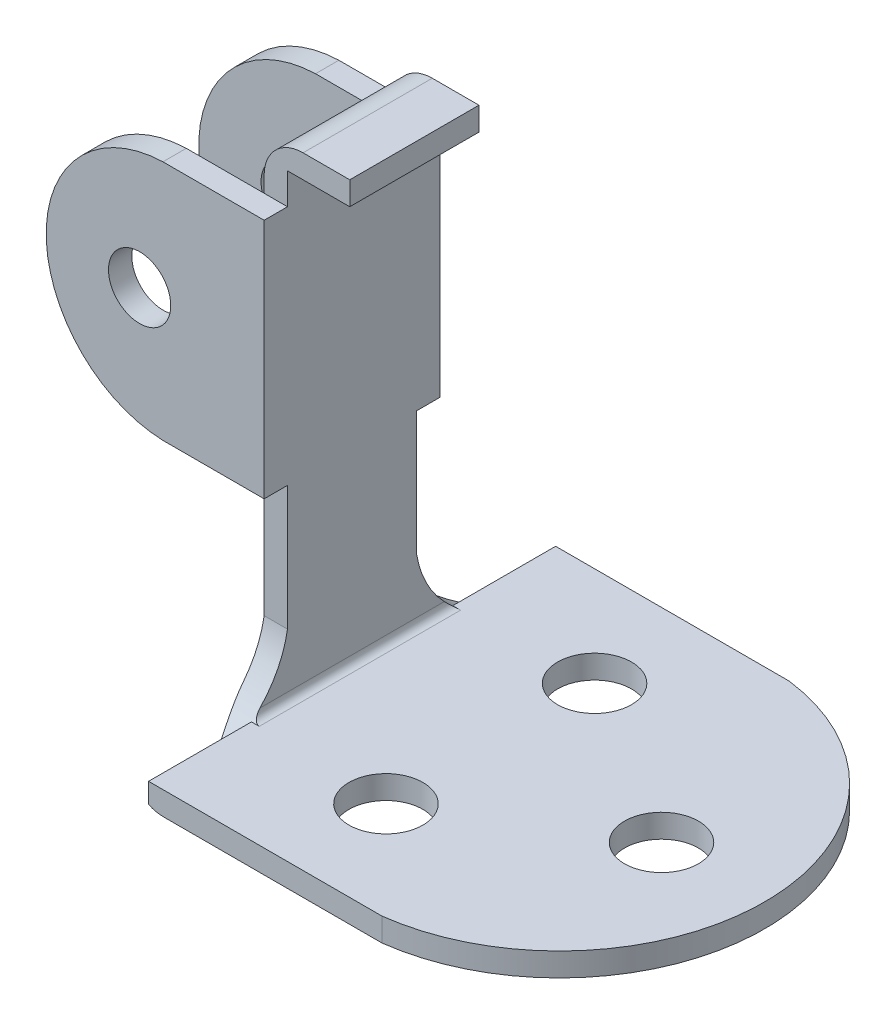
SolidWorks part; units mm, degrees
material "AISI 1020"
ref_plane "Front Plane" through (0, 0, 0) normal (0, 0, 1) x (1, 0, 0)
ref_plane "Top Plane" through (0, 0, 0) normal (0, 1, 0) x (1, 0, 0)
ref_plane "Right Plane" through (0, 0, 0) normal (1, 0, 0) x (0, 0, -1)
sketch "Sketch1" plane through (0, 0, 0) normal (0, 1, 0) x (1, 0, 0)
  line L0 (0, 26.15) -> (30, 26.15)
  line L3 (0, -26.15) -> (30, -26.15)
  line L4 (0, 26.15) -> (0, -26.15)
  line L5 (0, 0) -> (53, 0) construction
  line L6 (17.75, 15.4322) -> (17.75, 11.6834) construction
  line L7 (17.75, -12.5587) -> (17.75, -14.9746) construction
  line L8 (-11.0953, 1.0449) -> (-7.2792, 1.0449) construction
  line L9 (0, 9.3949) -> (-3, 9.3949) construction
  line L11 (0, -7.3051) -> (-3, -7.3051) construction
  line L12 (-3, 9.3949) -> (-3, -7.3051) construction
  arc A2 (30, 26.15) -> (30, -26.15) centre (26.6343, 0) cw
  circle A3 centre (17.75, 13.4) radius 4.75
  circle A5 centre (17.75, -13.4) radius 4.75
  circle A6 centre (39.75, 0) radius 4.75
  point P5 (0, 0)
  point P9 (53, 0)
  dimension "D4" = 9.5
  dimension "D5" = 12.75
  dimension "D1" = 52.3
  dimension "D2" = 53
  dimension "D3" = 30
  dimension "D6" = 13.25
  dimension "D7" = 12.75
  dimension "D8" = 17.75
  dimension "D9" = 16.7
  dimension "D10" = 3
extrude "Boss-Extrude1" add sketch "Sketch1" along normal blind 3
sketch "Sketch3" plane through (0, 0, 0) normal (-1, 0, 0) x (0, 0, 1)
  line L0 (-26.15, 0) -> (26.15, 0) construction
  line L1 (-8.3, 0) -> (8.3, 0)
  line L3 (-8.3, 62) -> (8.3, 62)
  line L5 (8.3, 0) -> (21.3, 0)
  line L6 (8.3, 0) -> (8.3, 11) construction
  line L7 (8.3, 62) -> (8.3, 11)
  line L8 (0, -1.8786) -> (0, 64.4627) construction
  line L9 (-8.3, 62) -> (-8.3, 11)
  line L10 (-8.3, 0) -> (-21.3, 0)
  arc A0 (21.3, 0) -> (8.3, 11) centre (21.3, 13.1818) cw
  arc A1 (-21.3, 0) -> (-8.3, 11) centre (-21.3, 13.1818) ccw
  point P6 (0, 0)
  dimension "D1" = 11
  dimension "D2" = 16.6
  dimension "D3" = 13
extrude "Boss-Extrude3" add sketch "Sketch3" along normal blind 3
sketch "Sketch4" plane through (0, 62, 0) normal (0, 1, 0) x (1, 0, 0)
  line L0 (-3, -8.3) -> (-3, 8.3) construction
  line L1 (-3, -8.3) -> (8, -8.3)
  line L2 (-3, -8.3) -> (-3, 8.3)
  line L3 (-3, 8.3) -> (8, 8.3)
  line L4 (8, -8.3) -> (8, 8.3)
  line L5 (-3, 8.3) -> (0, 8.3) construction
  dimension "D1" = 11
  dimension "D2" = 16.6
extrude "Boss-Extrude4" add sketch "Sketch4" along normal blind 3
sketch "Sketch5" plane through (0, 0, 8.3) normal (0, 0, 1) x (1, 0, 0)
  line L0 (0, 62) -> (0, 58) construction
  line L1 (0, 11) -> (0, 62) construction
  line L2 (0, 58) -> (0, 27)
  line L3 (0, 27) -> (-28, 27) construction
  line L4 (0, 58) -> (-28, 58) construction
  line L5 (-28, 27) -> (-28, 58) construction
  line L6 (0, 27) -> (-13, 27)
  line L7 (0, 58) -> (-13, 58)
  arc A0 (-13, 27) -> (-13, 58) centre (-12.4917, 42.5) cw
  circle A1 centre (-16, 42.5) radius 4
  point P11 (-28, 42.5)
  point P12 (-28, 42.5)
  dimension "D5" = 8
  dimension "D1" = 4
  dimension "D2" = 31
  dimension "D3" = 28
  dimension "D4" = 13
  dimension "D6" = 12
  dimension "D7" = 15.5
extrude "Boss-Extrude5" add sketch "Sketch5" along normal blind 3
mirror "Mirror1" about plane through (0, 0, 0) normal (0, 0, 1) of "Boss-Extrude5"
fillet "Fillet6" radius 5 2 edges at (-3, 65, 0) (-3, 0, 0)
fillet "Fillet7" radius 1 1 edges at (0, 3, 0)
sketch "Sketch7" plane through (0, 3, 0) normal (0, 1, 0) x (1, 0, 0)
  line L0 (39.75, 0) -> (53, 0) construction
  arc A0 (30, -26.15) -> (30, 26.15) centre (26.6343, 0) ccw construction
